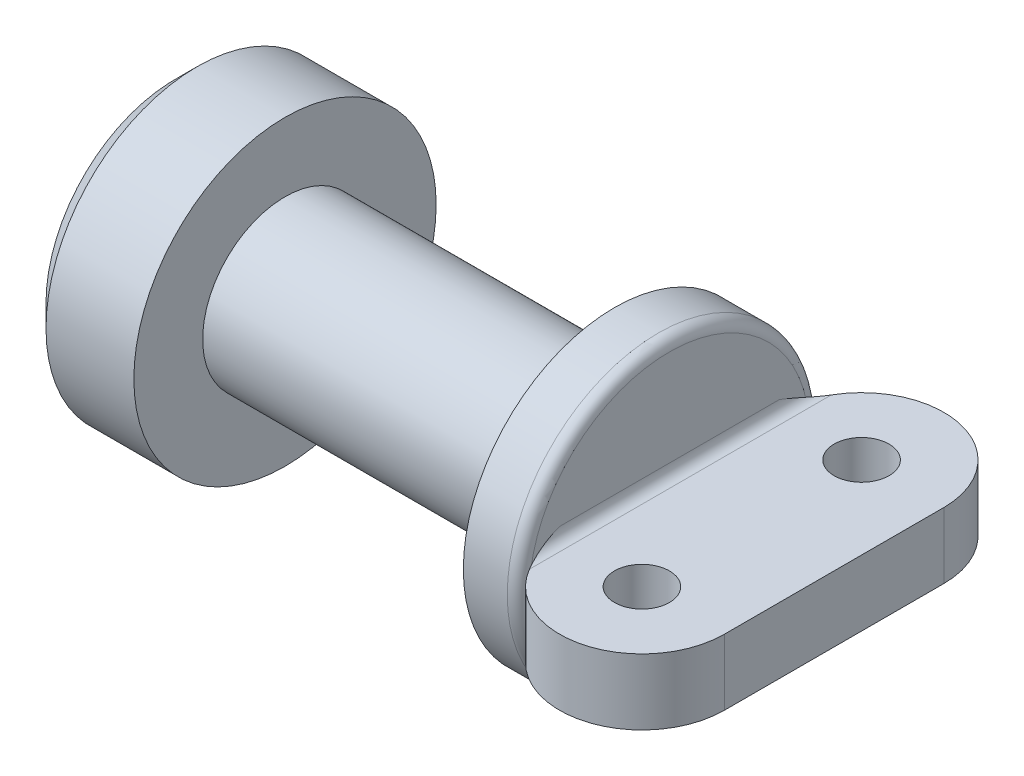
SolidWorks part; units mm, degrees
ref_plane "Front Plane" through (0, 0, 0) normal (0, 0, 1) x (1, 0, 0)
ref_plane "Top Plane" through (0, 0, 0) normal (0, 1, 0) x (1, 0, 0)
ref_plane "Right Plane" through (0, 0, 0) normal (1, 0, 0) x (0, 0, -1)
sketch "Sketch1" plane through (0, 0, 0) normal (1, 0, 0) x (0, 0, -1)
  circle A0 centre (0, 0) radius 0.75
  dimension "D1" = 1.5
extrude "Boss-Extrude1" add sketch "Sketch1" along normal blind 3
sketch "Sketch2" plane through (0, 0, 0) normal (-1, 0, 0) x (0, 0, 1)
  circle A0 centre (0, 0) radius 1.3762
extrude "Boss-Extrude2" add sketch "Sketch2" along normal blind 1
sketch "Sketch3" plane through (3, 0, 0) normal (1, 0, 0) x (0, 0, -1)
  circle A0 centre (0, 0) radius 1.3762
extrude "Boss-Extrude3" add sketch "Sketch3" along normal blind 0.5
sketch "Sketch4" plane through (3.5, 0, 0) normal (1, 0, 0) x (0, 0, -1)
  line L1 (-1, 0.3) -> (1, 0.3)
  line L2 (-1, 0.3) -> (-1, -0.3)
  line L3 (-1, -0.3) -> (1, -0.3)
  line L4 (1, 0.3) -> (1, -0.3)
  point P7 (-0.2559, 1.1662)
  point P9 (-1.5329, -0.0141)
  dimension "D1" = 0.3
  dimension "D2" = 0.3
  dimension "D3" = 1
extrude "Boss-Extrude4" add sketch "Sketch4" along normal blind 1.5
sketch "Sketch5" plane through (0, 0.3, 0) normal (0, 1, 0) x (1, 0, 0)
  line L0 (5, 1) -> (3.5, 1) construction
  line L1 (3.5, 1) -> (5.688, 1) construction
  line L2 (5, 1) -> (5, -1) construction
  line L3 (3.5, 1) -> (3.5, -1) construction
  line L4 (3.5, 0) -> (5, 0) construction
  arc A0 (5, 1) -> (3.5, 1) centre (4.25, 1) ccw
  circle A1 centre (4.25, 1) radius 0.25
  circle A2 centre (4.25, -1) radius 0.25
  arc A3 (5, -1) -> (3.5, -1) centre (4.25, -1) cw
  line M5 (3.5, 1) -> (3.5, -1)
  line M6 (3.5, -1) -> (5, -1)
  line M7 (5, -1) -> (5, 1)
  line M8 (5, 1) -> (3.5, 1)
  dimension "D1" = 0.5
extrude "Boss-Extrude5" add sketch "Sketch5" against normal blind 0.6 contours A1 A0 M8 | A3 A2 M6 | A2 A1 M6 M7 M8 M5 region at (4.25, 0.3, -1.3448) region at (4.25, 0.3, 0) region at (4.25, 0.3, 1.3448)
sketch "Sketch6" plane through (0, 0.3, 0) normal (0, 1, 0) x (1, 0, 0)
  line L0 (4.5, 1) -> (4, 1) construction
  line L1 (4.5, -1) -> (4, -1) construction
  circle A0 centre (4.25, 1) radius 0.25
  circle A1 centre (4.25, -1) radius 0.25
extrude "Cut-Extrude1" cut sketch "Sketch6" against normal through all both and the other way through all contours A0 | A1
chamfer "Chamfer1" distance 0.2 angle 45 1 edges at (-1, 0, 1.3762)
fillet "Fillet2" radius 0.1 1 edges at (3.5, 0.3, 0)
fillet "Fillet3" radius 0.1 1 edges at (3.5, -0.3, 0)
fillet "Fillet4" radius 0.1 1 edges at (3.5, 0, -1.3762)
